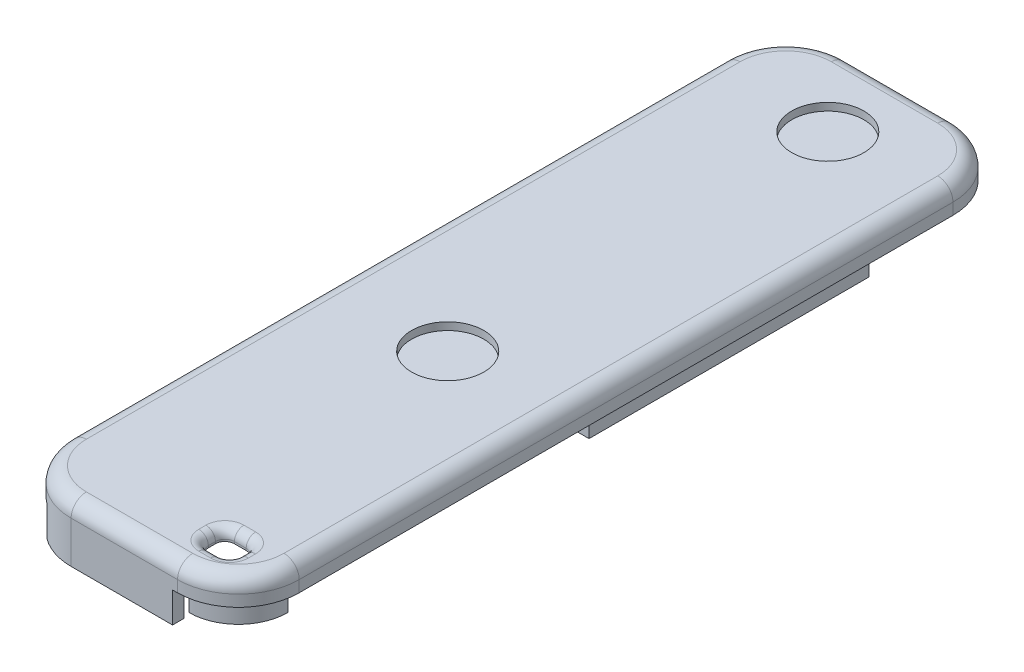
SolidWorks part; units mm, degrees
ref_plane "Front Plane" through (0, 0, 0) normal (0, 0, 1) x (1, 0, 0)
ref_plane "Top Plane" through (0, 0, 0) normal (0, 1, 0) x (1, 0, 0)
ref_plane "Right Plane" through (0, 0, 0) normal (1, 0, 0) x (0, 0, -1)
sketch "Sketch1" plane through (0, 0, 0) normal (0, 1, 0) x (1, 0, 0)
  line L1 (0, 0) -> (30, 0)
  line L2 (0, 0) -> (0, -102)
  line L3 (0, -102) -> (30, -102)
  line L4 (30, 0) -> (30, -102)
  dimension "D1" = 30
  dimension "D2" = 102
extrude "Boss-Extrude1" add sketch "Sketch1" along normal blind 3.5
fillet "Fillet1" radius 8 4 edges at (30, 1.75, 0) (30, 1.75, 102) (0, 1.75, 102) (0, 1.75, 0)
shell "Shell1" thickness 1.5 removed face at (15, 0, 51)
sketch "Sketch8" plane through (0, 2, 0) normal (0, -1, 0) x (1, 0, 0)
  line L0 (1.5, 17.5668) -> (3, 17.5668)
  line L1 (22, 100.5) -> (22, 99)
  line L3 (3, 17.5668) -> (3, 54.3754)
  line L4 (22, 1.5) -> (22, 3)
  line L5 (22, 3) -> (8, 3)
  line L6 (8, 3) -> (8, 1.5)
  line L8 (28.5, 8) -> (28.5, 94)
  line L9 (8, 1.5) -> (22, 1.5)
  line L10 (1.5, 94) -> (1.5, 8)
  line L11 (22, 100.5) -> (8, 100.5)
  line L12 (28.5, 17.5668) -> (28.5, 54.3754)
  line L13 (8, 1.5) -> (22, 1.5)
  line L14 (1.5, 54.3754) -> (1.5, 17.5668)
  line L17 (3, 54.3754) -> (1.5, 54.3754)
  line L19 (28.5, 54.3754) -> (27, 54.3754)
  line L20 (27, 54.3754) -> (27, 17.5668)
  line L21 (27, 17.5668) -> (28.5, 17.5668)
  line L24 (27, 94) -> (28.5, 94)
  line L25 (2.6165, 97.6425) -> (3.8588, 96.8019)
  line L27 (3, 94) -> (1.5, 94)
  arc A4 (27, 94) -> (22, 99) centre (22, 94) ccw
  arc A5 (3.8588, 96.8019) -> (3, 94) centre (8, 94) ccw
  arc A8 (22, 1.5) -> (28.5, 8) centre (22, 8) ccw
  arc A9 (1.5, 8) -> (8, 1.5) centre (8, 8) ccw
  arc A10 (8, 100.5) -> (1.5, 94) centre (8, 94) ccw
  arc A11 (28.5, 94) -> (22, 100.5) centre (22, 94) ccw
  arc A14 (2.6165, 97.6425) -> (1.5, 94) centre (8, 94) ccw
  arc A15 (28.5, 94) -> (22, 100.5) centre (22, 94) ccw
  dimension "D3" = 1.5
  dimension "D1" = 1.5
  dimension "D2" = 1.5
extrude "Boss-Extrude6" add sketch "Sketch8" along normal blind 5
fillet "Fillet5" radius 2 8 edges at (15, 3.5, 0) (27.6569, 3.5, 2.3431) (30, 3.5, 51) (27.6569, 3.5, 99.6569) (15, 3.5, 102) (2.3431, 3.5, 99.6569) (0, 3.5, 51) (2.3431, 3.5, 2.3431)
fillet "Fillet6" radius 1.25 23 edges at (3.2195, 2, 95.4653) (3.2376, 2, 97.2222) (4.9525, 2, 99.7413) (15, 2, 100.5) (22, 2, 99.75) (25.5355, 2, 97.5355) (27.75, 2, 94) (28.5, 2, 74.1877) (27.75, 2, 54.3754) (27, 2, 35.9711) (27.75, 2, 17.5668) (28.5, 2, 12.7834) (26.5962, 2, 3.4038) (22, 2, 2.25) (15, 2, 3) (8, 2, 2.25) (3.4038, 2, 3.4038) (1.5, 2, 12.7834) (2.25, 2, 17.5668) (3, 2, 35.9711) (2.25, 2, 54.3754) (1.5, 2, 74.1877) (2.25, 2, 94)
sketch "Sketch9" plane through (0, 3.5, 0) normal (0, 1, 0) x (1, 0, 0)
  line L0 (15.7494, -3.8138) -> (15.7494, -16.6138) construction
  line L2 (9.3494, -16.6138) -> (22.1494, -16.6138) construction
  line L3 (22.1494, -3.8138) -> (9.3494, -3.8138) construction
  circle A0 centre (15.7494, -10.2138) radius 4.75
  dimension "D1" = 9.5
extrude "Boss-Extrude8" add sketch "Sketch9" along normal blind 1
sketch "Sketch12" plane through (0, 4.5, 0) normal (0, 1, 0) x (1, 0, 0)
  circle A0 centre (15.7494, -10.2138) radius 4.75
  circle A1 centre (15.7494, -10.2138) radius 4.75 construction
  dimension "D1" = 9.5
extrude "Cut-Extrude3" cut sketch "Sketch12" against normal blind 2
pattern_linear "LPattern1" count 2 spacing 50 along (0, 0, 1) of "Cut-Extrude3", "Boss-Extrude8"
sketch "Sketch10" plane through (0, 3.5, 0) normal (0, 1, 0) x (1, 0, 0)
  line L1 (24.9479, -94.6749) -> (20.9053, -94.6749)
  line L2 (24.9479, -94.6749) -> (24.9479, -98.1096)
  line L3 (24.9479, -98.1096) -> (20.9053, -98.1096)
  line L4 (20.9053, -94.6749) -> (20.9053, -98.1096)
extrude "Cut-Extrude2" cut sketch "Sketch10" against normal up to next
fillet "Fillet7" radius 1.25 4 edges at (20.9053, 2.7452, 98.1096) (24.9479, 0.25, 98.1096) (24.9479, 2.75, 94.6749) (20.9053, 2.75, 94.6749)
fillet "Fillet8" radius 1.25 8 edges at (24.5818, 3.5, 95.0411) (24.9479, 3.5, 96.3923) (24.5818, 3.5, 97.7435) (22.9266, 3.5, 98.1096) (21.2714, 3.5, 97.7435) (20.9053, 3.5, 96.3923) (21.2714, 3.5, 95.0411) (22.9266, 3.5, 94.6749)
sketch "Sketch11" plane through (0, 0, 0) normal (0, -1, 0) x (1, 0, 0)
  line L0 (8, 100.5) -> (22, 100.5) construction
  line L1 (8, 102) -> (22, 102) construction
  line L2 (21.3405, 100.5) -> (21.3405, 102) construction
  line L3 (3.25, 98.4371) -> (3.25, 100.4372) construction
  line L4 (8, 100.5) -> (21.3405, 100.5)
  line L5 (8, 102) -> (21.3405, 102)
  line L6 (21.3405, 100.5) -> (21.3405, 102)
  line L7 (3.25, 98.4371) -> (3.25, 100.4372)
  arc A0 (8, 100.5) -> (2.6165, 97.6425) centre (8, 94) ccw construction
  arc A1 (8, 102) -> (0, 94) centre (8, 94) ccw construction
  arc A2 (8, 100.5) -> (3.25, 98.4371) centre (8, 94) ccw
  arc A3 (8, 102) -> (3.25, 100.4372) centre (8, 94) ccw
extrude "Boss-Extrude7" add sketch "Sketch11" along normal blind 4
